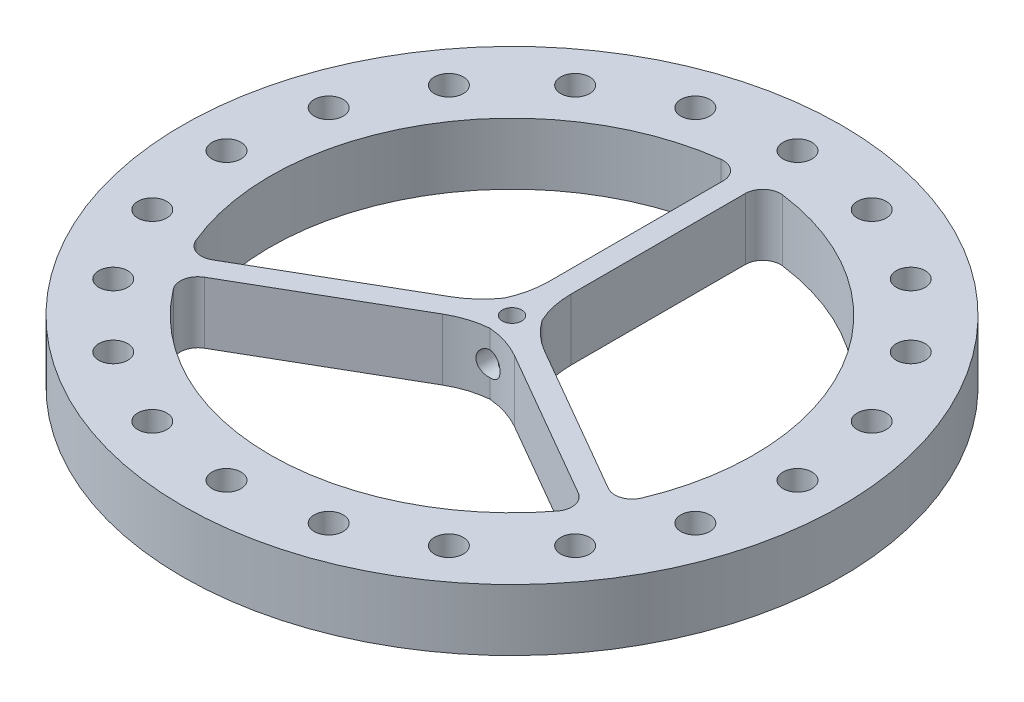
SolidWorks part; units mm, degrees
material "ABS"
ref_plane "Front Plane" through (0, 0, 0) normal (0, 0, 1) x (1, 0, 0)
ref_plane "Top Plane" through (0, 0, 0) normal (0, 1, 0) x (1, 0, 0)
ref_plane "Right Plane" through (0, 0, 0) normal (1, 0, 0) x (0, 0, -1)
sketch "Sketch1" plane through (0, 0, 0) normal (0, 1, 0) x (1, 0, 0)
  circle A0 centre (0, 0) radius 1.1
  circle A1 centre (0, 0) radius 2.5
  dimension "D1" = 2.2
  dimension "D2" = 5
extrude "Boss-Extrude1" add sketch "Sketch1" along normal blind 5
sketch "Sketch4" plane through (0, 0, 0) normal (0, 1, 0) x (1, 0, 0)
  circle A0 centre (0, 0) radius 27.5
  circle A1 centre (0, 0) radius 37.5
  dimension "D1" = 75
  dimension "D2" = 55
extrude "Boss-Extrude2" add sketch "Sketch4" along normal blind 5 separate body
sketch "Sketch5" plane through (0, 5, 0) normal (0, 1, 0) x (1, 0, 0)
  line L1 (-1.25, 27.5) -> (1.25, 27.5)
  line L2 (-1.25, 27.5) -> (-1.25, 2.1651)
  line L3 (-1.25, 2.1651) -> (1.25, 2.1651)
  line L4 (1.25, 27.5) -> (1.25, 2.1651)
  line L5 (-1.25, 27.5) -> (1.25, 2.1651) construction
  line L6 (-1.25, 2.1651) -> (1.25, 27.5) construction
  circle A0 centre (0, 0) radius 2.5 construction
  circle A2 centre (0, 0) radius 27.5 construction
  point P0 (0, 14.8325)
  point P9 (0, 27.5)
  point P10 (0, 27.5)
  dimension "D1" = 2.5
extrude "Boss-Extrude3" add sketch "Sketch5" against normal up to surface (5 mm away) up to face at (0, 0, 37.5)
pattern_circular "CirPattern1" count 3 over 360 about axis through (0, 5, 0) along (0, -1, 0) of "Boss-Extrude3"
sketch "Sketch6" plane through (0, 5, 0) normal (0, 1, 0) x (1, 0, 0)
  line L0 (1.25, 27.4716) -> (-1.25, 27.4716) construction
  line L1 (-1.25, 27.4716) -> (0, 27.4716) construction
  line L2 (0, 27.4716) -> (0, 37.5) construction
  circle A0 centre (0, 32.4858) radius 1.65
  circle A1 centre (0, 0) radius 37.5 construction
  point P5 (0, 32.4858)
  dimension "D1" = 3.3
extrude "Cut-Extrude1" cut sketch "Sketch6" against normal blind 5
fillet "Fillet1" radius 10 6 edges at (-2.5, 2.5, 0) (-1.25, 2.5, -2.1651) (1.25, 2.5, -2.1651) (2.5, 2.5, 0) (1.25, 2.5, 2.1651) (-1.25, 2.5, 2.1651)
fillet "Fillet2" radius 2 6 edges at (24.4161, 2.5, 12.6533) (-23.1661, 2.5, 14.8183) (23.1661, 2.5, 14.8183) (-1.25, 2.5, -27.4716) (-24.4161, 2.5, 12.6533) (1.25, 2.5, -27.4716)
pattern_circular "CirPattern2" count 20 over 360 about axis through (0, 5, 0) along (0, -1, 0) of "Cut-Extrude1"
sketch "Sketch7" plane through (0, 0, 0) normal (0, -1, 0) x (1, 0, 0)
  line L0 (11.0199, 33.9158) -> (7.9139, 33.2556)
  line L1 (0, 35.6612) -> (-2.75, 34.0735)
  line L2 (-2.75, 34.0735) -> (-2.75, 30.8981)
  line L3 (-2.75, 30.8981) -> (0, 29.3104)
  line L4 (0, 29.3104) -> (2.75, 30.8981)
  line L5 (2.75, 30.8981) -> (2.75, 34.0735)
  line L6 (2.75, 34.0735) -> (0, 35.6612)
  line L7 (7.9139, 33.2556) -> (6.9326, 30.2356)
  line L8 (6.9326, 30.2356) -> (9.0574, 27.8758)
  line L9 (9.0574, 27.8758) -> (12.1634, 28.536)
  line L10 (12.1634, 28.536) -> (13.1447, 31.556)
  line L11 (13.1447, 31.556) -> (11.0199, 33.9158)
  line L12 (20.9611, 28.8505) -> (17.8031, 29.1825)
  line L13 (17.8031, 29.1825) -> (15.9366, 26.6135)
  line L14 (15.9366, 26.6135) -> (17.2282, 23.7126)
  line L15 (17.2282, 23.7126) -> (20.3862, 23.3807)
  line L16 (20.3862, 23.3807) -> (22.2527, 25.9496)
  line L17 (22.2527, 25.9496) -> (20.9611, 28.8505)
  line L18 (28.8505, 20.9611) -> (25.9496, 22.2527)
  line L19 (25.9496, 22.2527) -> (23.3807, 20.3862)
  line L20 (23.3807, 20.3862) -> (23.7126, 17.2282)
  line L21 (23.7126, 17.2282) -> (26.6135, 15.9366)
  line L22 (26.6135, 15.9366) -> (29.1825, 17.8031)
  line L23 (29.1825, 17.8031) -> (28.8505, 20.9611)
  line L24 (33.9158, 11.0199) -> (31.556, 13.1447)
  line L25 (31.556, 13.1447) -> (28.536, 12.1634)
  line L26 (28.536, 12.1634) -> (27.8758, 9.0574)
  line L27 (27.8758, 9.0574) -> (30.2356, 6.9326)
  line L28 (30.2356, 6.9326) -> (33.2556, 7.9139)
  line L29 (33.2556, 7.9139) -> (33.9158, 11.0199)
  line L30 (35.6612, 0) -> (34.0735, 2.75)
  line L31 (34.0735, 2.75) -> (30.8981, 2.75)
  line L32 (30.8981, 2.75) -> (29.3104, 0)
  line L33 (29.3104, 0) -> (30.8981, -2.75)
  line L34 (30.8981, -2.75) -> (34.0735, -2.75)
  line L35 (34.0735, -2.75) -> (35.6612, 0)
  line L36 (33.9158, -11.0199) -> (33.2556, -7.9139)
  line L37 (33.2556, -7.9139) -> (30.2356, -6.9326)
  line L38 (30.2356, -6.9326) -> (27.8758, -9.0574)
  line L39 (27.8758, -9.0574) -> (28.536, -12.1634)
  line L40 (28.536, -12.1634) -> (31.556, -13.1447)
  line L41 (31.556, -13.1447) -> (33.9158, -11.0199)
  line L42 (28.8505, -20.9611) -> (29.1825, -17.8031)
  line L43 (29.1825, -17.8031) -> (26.6135, -15.9366)
  line L44 (26.6135, -15.9366) -> (23.7126, -17.2282)
  line L45 (23.7126, -17.2282) -> (23.3807, -20.3862)
  line L46 (23.3807, -20.3862) -> (25.9496, -22.2527)
  line L47 (25.9496, -22.2527) -> (28.8505, -20.9611)
  line L48 (20.9611, -28.8505) -> (22.2527, -25.9496)
  line L49 (22.2527, -25.9496) -> (20.3862, -23.3807)
  line L50 (20.3862, -23.3807) -> (17.2282, -23.7126)
  line L51 (17.2282, -23.7126) -> (15.9366, -26.6135)
  line L52 (15.9366, -26.6135) -> (17.8031, -29.1825)
  line L53 (17.8031, -29.1825) -> (20.9611, -28.8505)
  line L54 (11.0199, -33.9158) -> (13.1447, -31.556)
  line L55 (13.1447, -31.556) -> (12.1634, -28.536)
  line L56 (12.1634, -28.536) -> (9.0574, -27.8758)
  line L57 (9.0574, -27.8758) -> (6.9326, -30.2356)
  line L58 (6.9326, -30.2356) -> (7.9139, -33.2556)
  line L59 (7.9139, -33.2556) -> (11.0199, -33.9158)
  line L60 (0, -35.6612) -> (2.75, -34.0735)
  line L61 (2.75, -34.0735) -> (2.75, -30.8981)
  line L62 (2.75, -30.8981) -> (0, -29.3104)
  line L63 (0, -29.3104) -> (-2.75, -30.8981)
  line L64 (-2.75, -30.8981) -> (-2.75, -34.0735)
  line L65 (-2.75, -34.0735) -> (0, -35.6612)
  line L66 (-11.0199, -33.9158) -> (-7.9139, -33.2556)
  line L67 (-7.9139, -33.2556) -> (-6.9326, -30.2356)
  line L68 (-6.9326, -30.2356) -> (-9.0574, -27.8758)
  line L69 (-9.0574, -27.8758) -> (-12.1634, -28.536)
  line L70 (-12.1634, -28.536) -> (-13.1447, -31.556)
  line L71 (-13.1447, -31.556) -> (-11.0199, -33.9158)
  line L72 (-20.9611, -28.8505) -> (-17.8031, -29.1825)
  line L73 (-17.8031, -29.1825) -> (-15.9366, -26.6135)
  line L74 (-15.9366, -26.6135) -> (-17.2282, -23.7126)
  line L75 (-17.2282, -23.7126) -> (-20.3862, -23.3807)
  line L76 (-20.3862, -23.3807) -> (-22.2527, -25.9496)
  line L77 (-22.2527, -25.9496) -> (-20.9611, -28.8505)
  line L78 (-28.8505, -20.9611) -> (-25.9496, -22.2527)
  line L79 (-25.9496, -22.2527) -> (-23.3807, -20.3862)
  line L80 (-23.3807, -20.3862) -> (-23.7126, -17.2282)
  line L81 (-23.7126, -17.2282) -> (-26.6135, -15.9366)
  line L82 (-26.6135, -15.9366) -> (-29.1825, -17.8031)
  line L83 (-29.1825, -17.8031) -> (-28.8505, -20.9611)
  line L84 (-33.9158, -11.0199) -> (-31.556, -13.1447)
  line L85 (-31.556, -13.1447) -> (-28.536, -12.1634)
  line L86 (-28.536, -12.1634) -> (-27.8758, -9.0574)
  line L87 (-27.8758, -9.0574) -> (-30.2356, -6.9326)
  line L88 (-30.2356, -6.9326) -> (-33.2556, -7.9139)
  line L89 (-33.2556, -7.9139) -> (-33.9158, -11.0199)
  line L90 (-35.6612, 0) -> (-34.0735, -2.75)
  line L91 (-34.0735, -2.75) -> (-30.8981, -2.75)
  line L92 (-30.8981, -2.75) -> (-29.3104, 0)
  line L93 (-29.3104, 0) -> (-30.8981, 2.75)
  line L94 (-30.8981, 2.75) -> (-34.0735, 2.75)
  line L95 (-34.0735, 2.75) -> (-35.6612, 0)
  line L96 (-33.9158, 11.0199) -> (-33.2556, 7.9139)
  line L97 (-33.2556, 7.9139) -> (-30.2356, 6.9326)
  line L98 (-30.2356, 6.9326) -> (-27.8758, 9.0574)
  line L99 (-27.8758, 9.0574) -> (-28.536, 12.1634)
  line L100 (-28.536, 12.1634) -> (-31.556, 13.1447)
  line L101 (-31.556, 13.1447) -> (-33.9158, 11.0199)
  line L102 (-28.8505, 20.9611) -> (-29.1825, 17.8031)
  line L103 (-29.1825, 17.8031) -> (-26.6135, 15.9366)
  line L104 (-26.6135, 15.9366) -> (-23.7126, 17.2282)
  line L105 (-23.7126, 17.2282) -> (-23.3807, 20.3862)
  line L106 (-23.3807, 20.3862) -> (-25.9496, 22.2527)
  line L107 (-25.9496, 22.2527) -> (-28.8505, 20.9611)
  line L108 (-20.9611, 28.8505) -> (-22.2527, 25.9496)
  line L109 (-22.2527, 25.9496) -> (-20.3862, 23.3807)
  line L110 (-20.3862, 23.3807) -> (-17.2282, 23.7126)
  line L111 (-17.2282, 23.7126) -> (-15.9366, 26.6135)
  line L112 (-15.9366, 26.6135) -> (-17.8031, 29.1825)
  line L113 (-17.8031, 29.1825) -> (-20.9611, 28.8505)
  line L114 (-11.0199, 33.9158) -> (-13.1447, 31.556)
  line L115 (-13.1447, 31.556) -> (-12.1634, 28.536)
  line L116 (-12.1634, 28.536) -> (-9.0574, 27.8758)
  line L117 (-9.0574, 27.8758) -> (-6.9326, 30.2356)
  line L118 (-6.9326, 30.2356) -> (-7.9139, 33.2556)
  line L119 (-7.9139, 33.2556) -> (-11.0199, 33.9158)
  circle A0 centre (0, 32.4858) radius 2.75 construction
  circle A2 centre (0, 0) radius 37.5
  circle A3 centre (0, 0) radius 37.5
  point P129 (0, 0)
  dimension "D1" = 5.5
  dimension "D2" = 0
  dimension "D3" = 20
extrude "Boss-Extrude4" add sketch "Sketch7" along normal blind 2
sketch "Sketch8" plane through (0, 0, 0) normal (0, 1, 0) x (1, 0, 0)
  line L0 (-1.25, 5.4486) -> (-1.25, 25.292) construction
  line L1 (-22.5286, -11.5635) -> (-5.3436, -1.6418) construction
  line L4 (-4.0936, -3.8068) -> (-21.2786, -13.7286) construction
  line L5 (21.2786, -13.7286) -> (4.0936, -3.8068) construction
  line L6 (-1.25, 5.4486) -> (-1.25, 25.292)
  line L7 (-22.5286, -11.5635) -> (-5.3436, -1.6418)
  line L10 (-4.0936, -3.8068) -> (-21.2786, -13.7286)
  line L11 (21.2786, -13.7286) -> (4.0936, -3.8068)
  line L14 (1.25, 25.292) -> (1.25, 5.4486)
  line L15 (5.3436, -1.6418) -> (22.5286, -11.5635)
  line L16 (1.25, 25.292) -> (1.25, 5.4486)
  line L17 (5.3436, -1.6418) -> (22.5286, -11.5635)
  arc A0 (-1.25, 25.292) -> (-3.5049, 27.2757) centre (-3.25, 25.292) ccw construction
  arc A1 (-3.5049, 27.2757) -> (-25.3739, -10.6025) centre (0, 0) ccw construction
  arc A2 (-25.3739, -10.6025) -> (-22.5286, -11.5635) centre (-23.5286, -9.8314) ccw construction
  arc A3 (-5.3436, -1.6418) -> (-2.1722, 1.2541) centre (-10.3436, 7.0185) ccw construction
  arc A4 (-2.1722, 1.2541) -> (-1.25, 5.4486) centre (-11.25, 5.4486) ccw construction
  arc A9 (-21.2786, -13.7286) -> (-21.869, -16.6732) centre (-20.2786, -15.4606) ccw construction
  arc A10 (-21.869, -16.6732) -> (21.869, -16.6732) centre (0, 0) ccw construction
  arc A11 (21.869, -16.6732) -> (21.2786, -13.7286) centre (20.2786, -15.4606) ccw construction
  arc A12 (4.0936, -3.8068) -> (0, -2.5083) centre (-0.9064, -12.4671) ccw construction
  arc A13 (0, -2.5083) -> (-4.0936, -3.8068) centre (0.9064, -12.4671) ccw construction
  arc A14 (-1.25, 25.292) -> (-3.5049, 27.2757) centre (-3.25, 25.292) ccw
  arc A15 (-3.5049, 27.2757) -> (-25.3739, -10.6025) centre (0, 0) ccw
  arc A16 (-25.3739, -10.6025) -> (-22.5286, -11.5635) centre (-23.5286, -9.8314) ccw
  arc A17 (-5.3436, -1.6418) -> (-2.1722, 1.2541) centre (-10.3436, 7.0185) ccw
  arc A18 (-2.1722, 1.2541) -> (-1.25, 5.4486) centre (-11.25, 5.4486) ccw
  arc A23 (-21.2786, -13.7286) -> (-21.869, -16.6732) centre (-20.2786, -15.4606) ccw
  arc A24 (-21.869, -16.6732) -> (21.869, -16.6732) centre (0, 0) ccw
  arc A25 (21.869, -16.6732) -> (21.2786, -13.7286) centre (20.2786, -15.4606) ccw
  arc A26 (4.0936, -3.8068) -> (0, -2.5083) centre (-0.9064, -12.4671) ccw
  arc A27 (0, -2.5083) -> (-4.0936, -3.8068) centre (0.9064, -12.4671) ccw
  circle A29 centre (0, 0) radius 1.1
  circle A30 centre (0, 0) radius 1.1
  arc A35 (1.25, 5.4486) -> (2.1722, 1.2541) centre (11.25, 5.4486) ccw
  arc A36 (2.1722, 1.2541) -> (5.3436, -1.6418) centre (10.3436, 7.0185) ccw
  arc A37 (22.5286, -11.5635) -> (25.3739, -10.6025) centre (23.5286, -9.8314) ccw
  arc A38 (25.3739, -10.6025) -> (3.5049, 27.2757) centre (0, 0) ccw
  arc A39 (3.5049, 27.2757) -> (1.25, 25.292) centre (3.25, 25.292) ccw
  arc A40 (1.25, 5.4486) -> (2.1722, 1.2541) centre (11.25, 5.4486) ccw
  arc A41 (2.1722, 1.2541) -> (5.3436, -1.6418) centre (10.3436, 7.0185) ccw
  arc A42 (22.5286, -11.5635) -> (25.3739, -10.6025) centre (23.5286, -9.8314) ccw
  arc A43 (25.3739, -10.6025) -> (3.5049, 27.2757) centre (0, 0) ccw
  arc A44 (3.5049, 27.2757) -> (1.25, 25.292) centre (3.25, 25.292) ccw
  dimension "D1" = 0
  dimension "D2" = 0
extrude "Cut-Extrude2" cut sketch "Sketch8" against normal blind 3
sketch "Sketch9" plane through (0, 0, 0) normal (0, 0, 1) x (1, 0, 0)
  line L1 (0, -2) -> (0, 5) construction
  circle A0 centre (0, 1.5) radius 1.375
  point P2 (0, 4.7715)
  point P4 (0, -2)
  point P5 (0, 1.5)
  dimension "D1" = 2.75
extrude "Cut-Extrude3" cut sketch "Sketch9" along normal up to surface (27.4656 mm away) up to face at (0, 1.5, 22.0866)
